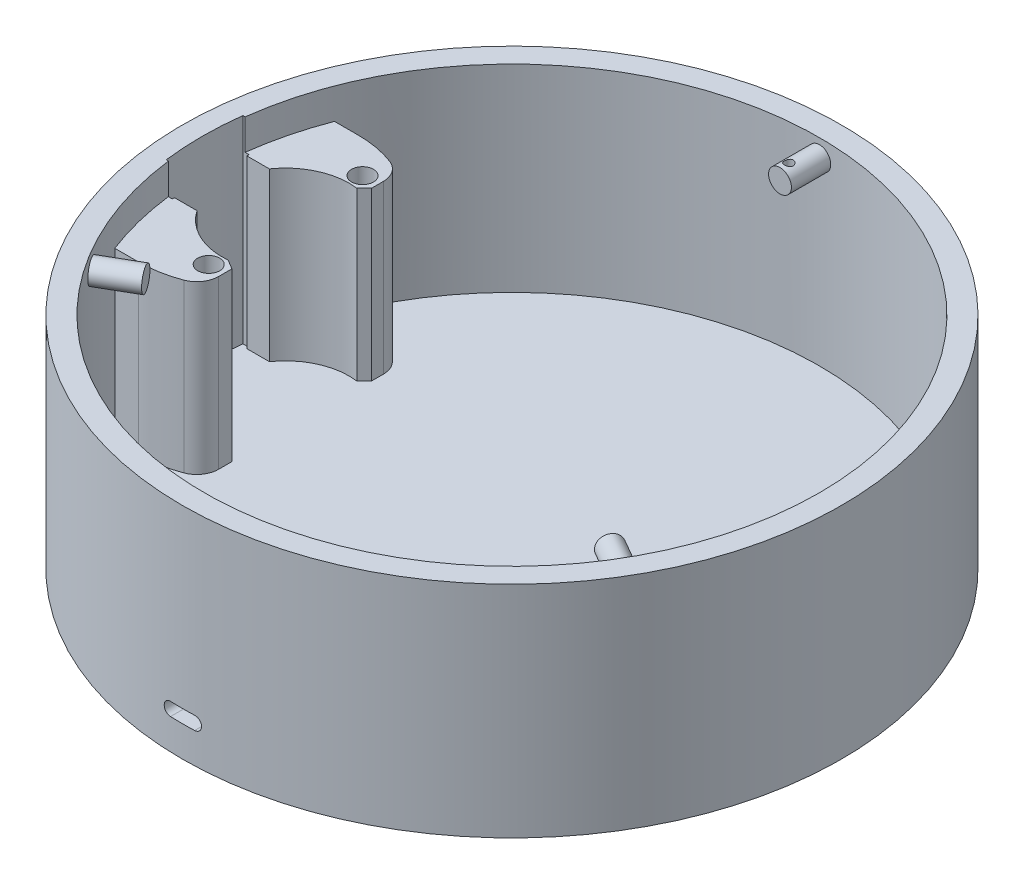
SolidWorks part; units mm, degrees
ref_plane "Front Plane" through (0, 0, 0) normal (0, 0, 1) x (1, 0, 0)
ref_plane "Top Plane" through (0, 0, 0) normal (0, 1, 0) x (1, 0, 0)
ref_plane "Right Plane" through (0, 0, 0) normal (1, 0, 0) x (0, 0, -1)
sketch "Sketch1" plane through (0, 0, 0) normal (0, 1, 0) x (1, 0, 0)
  circle A0 centre (0, 0) radius 75
  dimension "D1" = 150
extrude "Boss-Extrude1" add sketch "Sketch1" along normal blind 50
shell "Shell1" thickness 5 removed face at (0, 50, 75)
ref_plane "Plane1" through (0, 0, 75) normal (0, 0, 1) x (1, 0, 0)
sketch "Sketch2" plane through (0, 0, 75) normal (0, 0, 1) x (1, 0, 0)
  line L0 (-2.75, 8.5) -> (2.75, 8.5) construction
  line L1 (-2.75, 10) -> (2.75, 10)
  line L2 (-2.75, 7) -> (2.75, 7)
  line L3 (0, 0) -> (0, 17) construction
  line L4 (-75, 0) -> (75, 0) construction
  arc A0 (-2.75, 10) -> (-2.75, 7) centre (-2.75, 8.5) ccw
  arc A1 (2.75, 7) -> (2.75, 10) centre (2.75, 8.5) ccw
  point P2 (0, 8.5)
  dimension "D2" = 8.5
  dimension "D3" = 8.5
  dimension "D1" = 3
  dimension "D4" = 7
extrude "Cut-Extrude1" cut sketch "Sketch2" against normal up to next
ref_plane "Plane2" through (0, 0, -71) normal (0, 0, 1) x (1, 0, 0)
sketch "Sketch3" plane through (0, 0, -71) normal (0, 0, 1) x (1, 0, 0)
  line L0 (0, 0) -> (0, 92) construction
  line L1 (70, 50) -> (-70, 50) construction
  circle A0 centre (0, 46) radius 8
  circle A1 centre (0, 46) radius 2.6
  dimension "D1" = 16
  dimension "D2" = 5.2
  dimension "D3" = 4
extrude "Boss-Extrude2" add sketch "Sketch3" along normal blind 10 contours L0 A1 | A1 L0 region at (-1.1035, 46, -71) region at (1.1035, 46, -71)
pattern_circular "CirPattern1" count 3 over 360 about axis through (0, 50, 0) along (0, 1, 0) of "Boss-Extrude2"
sketch "Sketch11" plane through (0, 5, 0) normal (0, 1, 0) x (1, 0, 0)
  line L0 (-75, 0) -> (-60, 0) construction
  line L1 (-70.7107, 25) -> (-60, 25)
  line L2 (-70.7107, -25) -> (-60, -25)
  circle A0 centre (0, 0) radius 70 construction
  arc A2 (-60, -25) -> (-60, 25) centre (-60, 0) ccw
  circle A3 centre (0, 0) radius 75 construction
  arc A4 (-70.7107, 25) -> (-70.7107, -25) centre (0, 0) ccw
  point P4 (-70, 0)
  dimension "D2" = 25
  dimension "D1" = 35
extrude "Boss-Extrude6" add sketch "Sketch11" along normal blind 38
sketch "Sketch12" plane through (0, 43, 0) normal (0, 1, 0) x (1, 0, 0)
  line L0 (0, 0) -> (-43.5, 0) construction
  line L1 (0, 0) -> (0, 42.2101) construction
  dimension "D1" = 43.5
sketch "Sketch13" plane through (0, 43, 0) normal (0, 1, 0) x (1, 0, 0)
  line L7 (0, 0) -> (0, 42.2101) construction
  line L8 (-68.5, 0) -> (-51.5, 0) construction
  line L10 (-51.5, -17.5) -> (-51.5, 17.5) construction
  line L11 (-37.5, 0) -> (25, 0) construction
  circle A4 centre (-51.5, 17.5) radius 2.5
  circle A5 centre (-51.5, -17.5) radius 2.5
  line B0 (-55, 18) -> (-55, 13.5554)
  line B1 (-63.3216, 7.5) -> (-68.25, 7.5)
  line B2 (-68.5, 7.25) -> (-68.5, -7.25)
  line B3 (-68.25, -7.5) -> (-63.3216, -7.5)
  line B4 (-55, -13.5554) -> (-55, -18)
  line B5 (-48, -18) -> (-48, -13.5554)
  line B6 (-48, 13.5554) -> (-48, 18)
  arc B7 (-55, 13.5554) -> (-63.3216, 7.5) centre (-51.5, 0) ccw
  arc B8 (-68.25, 7.5) -> (-68.5, 7.25) centre (-68.25, 7.25) ccw
  arc B9 (-68.5, -7.25) -> (-68.25, -7.5) centre (-68.25, -7.25) ccw
  arc B10 (-63.3216, -7.5) -> (-55, -13.5554) centre (-51.5, 0) ccw
  arc B11 (-55, -18) -> (-48, -18) centre (-51.5, -18) ccw
  arc B12 (-48, -13.5554) -> (-48, 13.5554) centre (-51.5, 0) ccw
  arc B13 (-48, 18) -> (-55, 18) centre (-51.5, 18) ccw
  dimension "D4" = 5
  dimension "D5" = 35
  dimension "D3" = 5
  dimension "D6" = 35
  dimension "D7" = 17.5
sketch_block_instance "Block1-1"
sketch_block "Block1"
extrude "Cut-Extrude7" cut sketch "Sketch13" against normal blind 5 contours A4 | A5 region at (-51.5, 43, -17.5)
sketch "Sketch14" plane through (0, 43, 0) normal (0, 1, 0) x (1, 0, 0)
  circle A0 centre (-43.5, 0) radius 2.5
  dimension "D1" = 5
extrude "Cut-Extrude8" cut sketch "Sketch14" against normal blind 5
sketch "Sketch15" plane through (0, 43, 0) normal (0, 1, 0) x (1, 0, 0)
  line L0 (-48, 14.0712) -> (-48, 21.9317)
  line L1 (-48, -14.0712) -> (-48, -21.9317)
  line L2 (-51.5, -17.5) -> (-51.5, 17.5) construction
  line L4 (-63.4334, -8.2368) -> (-69.0626, -8.2368)
  line L6 (-63.4334, 8.2368) -> (-69.0626, 8.2368)
  line L7 (-69.0626, -8.2368) -> (-69.0626, 8.2368)
  line L8 (-65.2062, 4.7318) -> (-69.0626, 8.2368) construction
  line L9 (-65.2062, -4.7318) -> (-69.0626, -8.2368) construction
  arc A0 (-60, -25) -> (-60, 25) centre (-60, 0) ccw construction
  arc A1 (-60, -25) -> (-60, 25) centre (-60, 0) ccw construction
  arc A2 (-48, 14.0712) -> (-63.4334, 8.2368) centre (-51.5, 0) ccw
  arc A3 (-48, -21.9317) -> (-48, 21.9317) centre (-60, 0) ccw
  arc A4 (-63.4334, -8.2368) -> (-48, -14.0712) centre (-51.5, 0) ccw
  dimension "D1" = 29
extrude "Cut-Extrude9" cut sketch "Sketch15" against normal up to surface (38 mm away) up to face at (-22.5959, 5, 0)
chamfer "Chamfer1" distance 2 angle 45 2 edges at (-48, 24, -14.0712) (-48, 24, 14.0712) first distance on face at (-48, 24, -18.0015) first distance on face at (-56.1721, 24, 12.3586)
fillet "Fillet1" radius 5 2 edges at (-48, 24, 21.9317) (-48, 24, -21.9317)
sketch "Sketch16" plane through (0, 50, 0) normal (0, 1, 0) x (1, 0, 0)
  line L0 (-69.0626, 0) -> (-51.9198, 0) construction
  line L1 (-69.0626, -8.2368) -> (-69.0626, 8.2368) construction
  line L2 (-69.0626, 8.2368) -> (-69.5137, 8.2368)
  line L3 (-69.0626, -8.2368) -> (-69.5137, -8.2368)
  line L4 (-69.0626, -8.2368) -> (-69.0626, 8.2368)
  line L5 (-68.5626, -8.7368) -> (-69.9565, -8.7368)
  line L6 (-68.5626, -8.7368) -> (-68.5626, 8.7368)
  line L7 (-68.5626, 8.7368) -> (-69.9565, 8.7368)
  arc A0 (-65.3835, 25) -> (-65.3835, -25) centre (0, 0) ccw construction
  arc A1 (-69.5137, 8.2368) -> (-69.5137, -8.2368) centre (0, 0) ccw
  arc A2 (-69.9565, 8.7368) -> (-69.9565, -8.7368) centre (0, 0) ccw
  dimension "D1" = 0.5
extrude "Cut-Extrude10" cut sketch "Sketch16" against normal up to surface (45 mm away) contours A2 L5 L6 L7 up to face at (-48.4246, 5, -0.0262)
ref_plane "Plane3" through (0, 60, 0) normal (0, 1, 0) x (1, 0, 0)
sketch "Sketch18" plane through (0, 60, 0) normal (0, 1, 0) x (1, 0, 0)
  line L0 (0, 0) -> (0, 66.9693) construction
  circle A0 centre (0, 63) radius 1
  point P5 (0, 63)
  dimension "D2" = 2
  dimension "D1" = 63
extrude "Cut-Extrude11" cut sketch "Sketch18" against normal up to next
